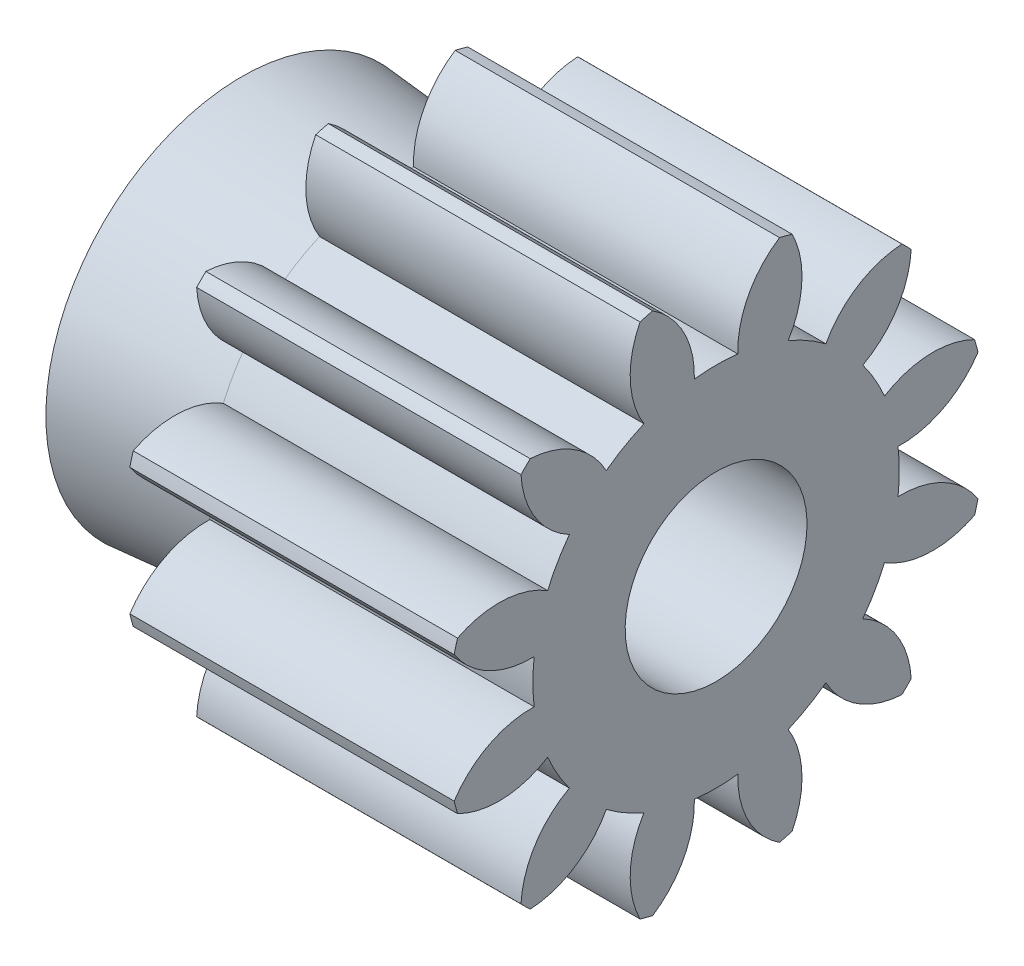
SolidWorks part; units mm, degrees
ref_plane "Plane1" through (0, 0, 0) normal (0, 0, 1) x (1, 0, 0)
ref_plane "Plane2" through (0, 0, 0) normal (0, 1, 0) x (1, 0, 0)
ref_plane "Plane3" through (0, 0, 0) normal (1, 0, 0) x (0, 0, -1)
sketch "HoldingSke" plane through (0, 0, 0) normal (0, 1, 0) x (1, 0, 0)
  line L0 (0, 0) -> (496.899, -105.6191)
  line L1 (-15, 0) -> (100, 0) construction
  line L2 (0, 0) -> (-2.1039, 2.3779)
  line L3 (0, 0) -> (-11.863, 4.5341)
  line L4 (0, 0) -> (8.4473, 1.7955)
  line L5 (0, 0) -> (-47.5972, -17.7524)
  line L6 (0, 0) -> (-10.5278, -7.1032)
  line L7 (-2.1039, 2.3779) -> (8.8308, 51.9871)
  line L8 (-76.2, 54.61) -> (-69.596, 54.61)
  line L9 (-71.009, 38.7566) -> (-53.1078, 45.2721)
  line L10 (-76.2, 71.12) -> (104.1128, 71.12)
  line L11 (0, 0) -> (-12.7, 0)
  line L12 (-76.2, 101.6) -> (-76.1492, 101.6)
  line L13 (24.9733, 27.94) -> (52.9518, 28.4284)
  line L14 (24.9733, 27.94) -> (25.0241, 27.9398)
  line L15 (24.9733, 27.94) -> (100.4021, 29.52)
  circle A0 centre (0, 0) radius 3.175
  circle A1 centre (0, 0) radius 6.0452
  circle A2 centre (0, 0) radius 38.1
  circle A3 centre (0, 0) radius 3.175
  dimension "Num_teeth" = 12
  dimension "H" = 19.05
  dimension "Pitch_radius" = 180.3128
  dimension "Width" = 12.7
  dimension "Thickness" = 12.7
sketch "BasProSke" plane through (0, 0, 0) normal (0, 1, 0) x (1, 0, 0)
  line L0 (-10, 0) -> (60, 0) construction
  line L1 (0, 0) -> (0, 8.89)
  line L2 (0, 0) -> (12.7, 0)
  line L3 (12.7, 0) -> (12.7, 8.89)
  line L4 (12.7, 8.89) -> (0, 8.89)
  dimension "Thickness" = 12.7
  dimension "Diameter" = 17.78
revolve "Base-Revolve" add sketch "BasProSke" angle 360 about L0
sketch "TooCutSke" plane through (0, 0, 0) normal (1, 0, 0) x (0, 0, -1)
  line L1 (0, 0) -> (0, 107) construction
  line L2 (0, 0) -> (-1.0834, 7.5426) construction
  line L3 (0, 0) -> (-3.9164, 14.6164) construction
  line L4 (-1.0834, 7.5426) -> (-1.9582, 7.3082) construction
  arc A0 (0.7171, 6.0025) -> (-0.7171, 6.0025) centre (0, 0) ccw
  arc A1 (2.1216, 8.6593) -> (-2.1216, 8.6593) centre (0, 0) ccw
  circle A2 centre (0, 0) radius 7.62 construction
  circle A3 centre (0, 0) radius 7.1605 construction
  arc A4 (-0.7171, 6.0025) -> (-2.1216, 8.6593) centre (-3.7638, 6.0915) ccw
  arc A5 (2.1216, 8.6593) -> (0.7171, 6.0025) centre (3.7638, 6.0915) ccw
extrude "ToothCut" cut sketch "TooCutSke" along normal through all
fillet "Breaks" [suppressed] radius 0.0254 tangent propagation no
fillet "RootFillets" [suppressed] radius 0.3048
pattern_circular "TeethCuts" count 12 every 30 about axis through (-10, 0, 0) along (1, 0, 0) of "ToothCut", "RootFillets", "Breaks"
sketch "HubNeaOneSke" plane through (0, 0, 0) normal (-1, 0, 0) x (0, 0, 1)
  circle A0 centre (0, 0) radius 6.0452
  dimension "Diameter" = 12.0904
extrude "HubNearOne" [suppressed] add sketch "HubNeaOneSke" along normal blind 38.1001
sketch "HubNeaBotSke" plane through (0, 0, 0) normal (-1, 0, 0) x (0, 0, 1)
  circle A0 centre (0, 0) radius 6.0452
  dimension "Diameter" = 12.0904
extrude "HubNearBoth" [suppressed] add sketch "HubNeaBotSke" along normal blind 19.05
ref_plane "FarPln" through (12.7, 0, 0) normal (1, 0, 0) x (0, 0, -1)
sketch "HubFarSke" plane through (12.7, 0, 0) normal (1, 0, 0) x (0, 0, -1)
  circle A0 centre (0, 0) radius 6.0452
  dimension "Diameter" = 12.0904
extrude "HubFar" [suppressed] add sketch "HubFarSke" along normal blind 19.05
sketch "BorSke" plane through (0, 0, 0) normal (1, 0, 0) x (0, 0, -1)
  circle A0 centre (0, 0) radius 3
  dimension "D1" = 6
extrude "Bore" cut sketch "BorSke" along normal mid plane 101.6001
sketch "KeySke" plane through (0, 0, 0) normal (1, 0, 0) x (0, 0, -1)
  line L0 (-0.127, 0) -> (-0.127, 3.429)
  line L1 (-0.127, 3.429) -> (0.127, 3.429)
  line L2 (0.127, 3.429) -> (0.127, 0)
  line L3 (0, 0) -> (0, 34) construction
  line L4 (-0.127, 0) -> (0.127, 0)
  dimension "Width" = 0.254
extrude "Keyway" [suppressed] cut sketch "KeySke" along normal mid plane 101.6001
pattern_circular "Keyway2" [suppressed] count 2 every 90 about axis through (-10, 0, 0) along (1, 0, 0) reverse direction yes
sketch "Sketch1" plane through (0, 0, 0) normal (0, 0, 1) x (1, 0, 0)
  line L0 (0, 0) -> (-2.5422, 0) construction
  line L1 (0, -4.46) -> (-4.95, -4.46)
  line L2 (-4.95, -4.46) -> (-4.95, -6.46)
  line L3 (-4.95, -6.46) -> (0, -6.0452)
  line L4 (0, -6.0452) -> (0, -4.46)
  dimension "D1" = 2
  dimension "D2" = 4.46
  dimension "D3" = 4.95
revolve "Revolve1" add sketch "Sketch1" angle 360 about L0
sketch "Sketch2" plane through (0, 0, 0) normal (0, 0, 1) x (1, 0, 0)
  line L0 (12.7, -8.6403) -> (0, -8.6403) construction
  line L1 (12.7, 8.6403) -> (10.7, 8.6403)
  line L2 (12.7, 8.6403) -> (12.7, -8.6403)
  line L3 (12.7, -8.6403) -> (10.7, -8.6403)
  line L4 (10.7, 8.6403) -> (10.7, -8.6403)
  dimension "D1" = 2
extrude "Cut-Extrude1" cut sketch "Sketch2" against normal through all both and the other way through all
equation "' \"Pitch@HoldingSke\" = 4"
equation "' \"Num_teeth@HoldingSke\" = 12"
equation "' \"Ap@HoldingSke\" =  20"
equation "' \"Ap@HoldingSke\" = 20"
equation "' \"Width@HoldingSke\" = 0.5"
equation "' \"Hub_dia@HoldingSke\"= 1"
equation "' \"Hub_dia@HoldingSke\" = 1"
equation "' \"Overall_len@HoldingSke\" = 1.0"
equation "' \"Bore@HoldingSke\" = 0.75"
equation "' \"T_dim@HoldingSke\" = 0.85"
equation "' \"Width@KeySke\" = 0.25"
equation "' \"Show_teeth@HoldingSke\" = 13"
equation "' \"Backlash@HoldingSke\" = 0.009"
equation "' \"Addendum_fac@HoldingSke\" = 1.0"
equation "' \"Dedendum_fac@HoldingSke\" = 1.25"
equation "' \"Dedendum_add@HoldingSke\" = 0.00005"
equation "' \"Clearance_fac@HoldingSke\" = 0.25"
equation "' \"Pitch@HoldingSke\" = 0.5"
equation "' \"Num_teeth@HoldingSke\" = 23"
equation "' \"Show_teeth@HoldingSke\" = 23"
equation "' \"Backlash@HoldingSke\" = 0.0375"
equation "\"Overcut_dia@TooCutSke\" = (\"Num_teeth@HoldingSke\" + 2 * \"Addendum_fac@HoldingSke\") / \"Pitch@HoldingSke\" + 0.002"
equation "\"Pitch_dia@TooCutSke\" = \"Num_teeth@HoldingSke\" / \"Pitch@HoldingSke\""
equation "\"Base_dia@TooCutSke\" = \"Num_teeth@HoldingSke\" / \"Pitch@HoldingSke\" * cos((\"Ap@HoldingSke\"  * 3.14159265 / 180))"
equation "\"Root_dia@TooCutSke\" = (\"Num_teeth@HoldingSke\" + 2) / \"Pitch@HoldingSke\" - 2 * (\"Addendum_fac@HoldingSke\" + \"Dedendum_fac@HoldingSke\") / \"Pitch@HoldingSke\" - \"Dedendum_add@HoldingSke\" * 2"
equation "\"Half_ang@TooCutSke\" = 180 / \"Num_teeth@HoldingSke\""
equation "\"Half_CT@TooCutSke\" = \"Num_teeth@HoldingSke\" / \"Pitch@HoldingSke\" * sin((3.14159265 / 2 / \"Num_teeth@HoldingSke\")) / 2 - 7 * \"Backlash@HoldingSke\" / 4"
equation "\"Flank_rad@TooCutSke\" = \"Num_teeth@HoldingSke\" / \"Pitch@HoldingSke\" / 5"
equation "\"Radius@RootFillets\" = \"Clearance_fac@HoldingSke\" / \"Pitch@HoldingSke\" + \"Dedendum_add@HoldingSke\""
equation "\"Break_rad@Breaks\" = 0.02 / \"Pitch@HoldingSke\""
equation "\"Thickness@HoldingSke\" = \"Width@HoldingSke\""
equation "\"OAL@HoldingSke\" = \"Thickness@HoldingSke\""
equation "\"MHD@HoldingSke\" = (\"Num_teeth@HoldingSke\" + 2) / \"Pitch@HoldingSke\" - 2 * (\"Addendum_fac@HoldingSke\" + \"Dedendum_fac@HoldingSke\")  / \"Pitch@HoldingSke\" - \"Dedendum_add@HoldingSke\" * 2"
equation "\"MBD@HoldingSke\" = (\"Num_teeth@HoldingSke\" + 2) / \"Pitch@HoldingSke\" - 2 * (\"Addendum_fac@HoldingSke\" + \"Dedendum_fac@HoldingSke\")  / \"Pitch@HoldingSke\" - \"Dedendum_add@HoldingSke\" * 2 - 0.002"
equation "\"MHD@HoldingSke\" = ((sgn( \"MHD@HoldingSke\" - \"Hub_dia@HoldingSke\" )-1)*( \"MHD@HoldingSke\" - \"Hub_dia@HoldingSke\" ))/-2+ \"Hub_dia@HoldingSke\""
equation "\"MBD@HoldingSke\" = ((sgn( \"MBD@HoldingSke\" - \"Bore@HoldingSke\" )-1)*( \"MBD@HoldingSke\" - \"Bore@HoldingSke\" ))/-2+ \"Bore@HoldingSke\""
equation "\"OAL@HoldingSke\" = ((sgn( \"OAL@HoldingSke\" - \"Overall_len@HoldingSke\" )+1)*( \"OAL@HoldingSke\" - \"Overall_len@HoldingSke\" ))/2 + \"Overall_len@HoldingSke\" + 0.000002"
equation "\"Num_teeth@TeethCuts\" = int( \"Show_teeth@HoldingSke\" ) + 1"
equation "\"Num_teeth@TeethCuts\" = ((sgn( \"Num_teeth@TeethCuts\" - \"Num_teeth@HoldingSke\" )-1)*( \"Num_teeth@TeethCuts\" - \"Num_teeth@HoldingSke\" ))/-2+ \"Num_teeth@HoldingSke\""
equation "\"Num_teeth@TeethCuts\" = ((sgn( \"Num_teeth@TeethCuts\" - 2.0)+1)*( \"Num_teeth@TeethCuts\" - 2.0))/2 +2.0"
equation "\"Angle@TeethCuts\" = 360.0 / \"Num_teeth@HoldingSke\""
equation "\"Diameter@BasProSke\" = (\"Num_teeth@HoldingSke\" + 2 * \"Addendum_fac@HoldingSke\") / \"Pitch@HoldingSke\""
equation "\"Thickness@BasProSke\"  = \"Thickness@HoldingSke\""
equation "' \"Fillet_rad@BasProSke\" =  \"Thickness@HoldingSke\" * 0.05"
equation "' \"Fillet_rad@BasProSke\" = \"Thickness@HoldingSke\" * 0.05"
equation "\"MHD@HoldingSke\" = ((sgn( \"MHD@HoldingSke\" - \"Root_dia@TooCutSke\" )-1)*( \"MHD@HoldingSke\" - \"Root_dia@TooCutSke\" ))/-2+ \"Root_dia@TooCutSke\""
equation "\"Diameter@HubNeaOneSke\" = \"MHD@HoldingSke\""
equation "\"Length@HubNearOne\" = \"OAL@HoldingSke\" - \"Thickness@BasProSke\""
equation "\"Diameter@HubNeaBotSke\" = \"MHD@HoldingSke\""
equation "\"Length@HubNearBoth\" = ( \"OAL@HoldingSke\" - \"Thickness@BasProSke\" ) / 2.0"
equation "\"Thickness@FarPln\" = \"Thickness@BasProSke\""
equation "\"Diameter@HubFarSke\" = \"MHD@HoldingSke\""
equation "\"Length@HubFar\" = ( \"OAL@HoldingSke\" - \"Thickness@BasProSke\" ) / 2.0"
equation "\"D1@Bore\" = \"OAL@HoldingSke\" * 2.0"
equation "\"D1@Keyway\" = \"OAL@HoldingSke\" * 2.0"
equation "\"Offset@KeySke\" = \"T_dim@HoldingSke\" - \"MBD@HoldingSke\" / 2.0"
